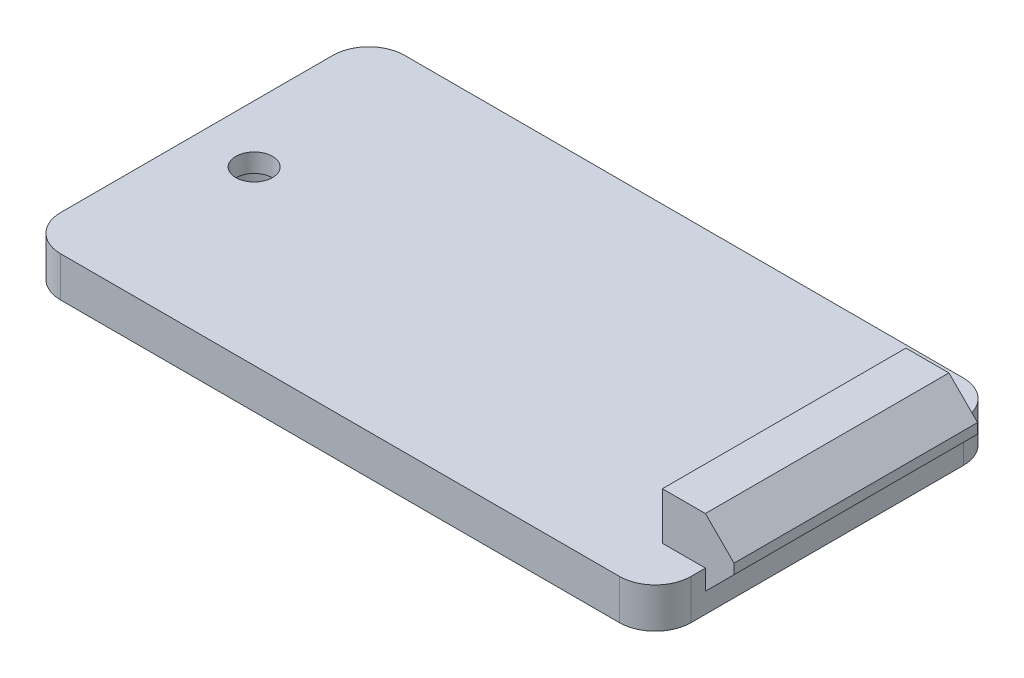
SolidWorks part; units mm, degrees
ref_plane "Front Plane" through (0, 0, 0) normal (0, 0, 1) x (1, 0, 0)
ref_plane "Top Plane" through (0, 0, 0) normal (0, 1, 0) x (1, 0, 0)
ref_plane "Right Plane" through (0, 0, 0) normal (1, 0, 0) x (0, 0, -1)
sketch "Sketch1" plane through (0, 0, 0) normal (0, 1, 0) x (1, 0, 0)
  line L0 (0, 15.24) -> (55.88, 15.24) construction
  line L1 (3.175, 0) -> (52.705, 0)
  line L2 (0, 3.175) -> (0, 27.305)
  line L3 (3.175, 30.48) -> (52.705, 30.48)
  line L4 (55.88, 3.175) -> (55.88, 27.305)
  arc A0 (3.175, 30.48) -> (0, 27.305) centre (3.175, 27.305) ccw
  arc A1 (55.88, 27.305) -> (52.705, 30.48) centre (52.705, 27.305) ccw
  arc A2 (52.705, 0) -> (55.88, 3.175) centre (52.705, 3.175) ccw
  arc A3 (0, 3.175) -> (3.175, 0) centre (3.175, 3.175) ccw
  circle A4 centre (5.08, 15.24) radius 1.632
  dimension "D3" = 6.35
  dimension "D1" = 3.2639
  dimension "D2" = 5.08
  dimension "D4" = 3.175
  dimension "D5" = 3.175
  dimension "D6" = 49.53
  dimension "D7" = 24.13
extrude "Boss-Extrude1" add sketch "Sketch1" along normal blind 3.556
sketch "Sketch2" plane through (0, 0, 0) normal (0, -1, 0) x (1, 0, 0)
  circle A0 centre (5.08, -15.24) radius 3.175
  circle A1 centre (5.08, -15.24) radius 1.6319
  dimension "D1" = 6.35
extrude "Cut-Extrude1" cut sketch "Sketch2" against normal blind 1.905
sketch "Sketch3" plane through (55.88, 0, 0) normal (1, 0, 0) x (0, 0, -1)
  line L0 (3.175, 3.556) -> (3.175, 0) construction
  line L1 (4.445, 1.5875) -> (26.035, 1.5875)
  line L2 (4.445, 1.5875) -> (4.445, 7.9375)
  line L3 (4.445, 7.9375) -> (26.035, 7.9375)
  line L4 (26.035, 1.5875) -> (26.035, 7.9375)
  line L5 (27.305, 3.556) -> (27.305, 0) construction
  line L6 (3.175, 0) -> (27.305, 0) construction
  dimension "D1" = 1.27
  dimension "D2" = 1.27
  dimension "D3" = 1.5875
  dimension "D4" = 6.35
extrude "Boss-Extrude2" add sketch "Sketch3" along normal blind 2.54
chamfer "Chamfer1" distance 2.7305 angle 45 2 edges at (58.42, 1.5875, -15.24) (58.42, 7.9375, -15.24)
sketch "Sketch4" plane through (55.88, 0, 0) normal (-1, 0, 0) x (0, 0, 1)
  line L5 (-26.035, 7.747) -> (-4.445, 7.747)
  line L6 (-26.035, 7.747) -> (-26.035, 3.556)
  line L7 (-26.035, 3.556) -> (-4.445, 3.556)
  line L8 (-4.445, 7.747) -> (-4.445, 3.556)
extrude "Boss-Extrude3" add sketch "Sketch4" along normal blind 3.81
sketch "Sketch5" plane through (0, 0, 0) normal (0, -1, 0) x (1, 0, 0)
  line L0 (12.7, -9.9279) -> (12.7, -30.48) construction
  line L2 (52.705, -30.48) -> (3.175, -30.48) construction
  line L3 (0, -27.305) -> (0, -3.175) construction
  line L4 (0, -15.24) -> (55.88, -15.24) construction
  line L5 (55.88, -26.035) -> (55.88, -4.445) construction
  line L6 (11.1125, -8.89) -> (11.1433, -21.9013)
  line L7 (14.2875, -8.89) -> (14.2567, -21.9013)
  arc A0 (14.2875, -8.89) -> (11.1125, -8.89) centre (12.7, -8.89) ccw
  arc A1 (11.1433, -21.9013) -> (14.2567, -21.9013) centre (12.7, -21.59) ccw
  dimension "D2" = 3.175
  dimension "D3" = 3.175
  dimension "D1" = 12.7
  dimension "D4" = 12.7
  dimension "D5" = 6.35
extrude "Cut-Extrude2" cut sketch "Sketch5" against normal blind 1.778
sketch "Sketch6" plane through (0, 0, 0) normal (0, -1, 0) x (1, 0, 0)
  line L0 (14.2807, -11.7475) -> (55.88, -11.7475) construction
  line L1 (14.2567, -21.9013) -> (14.2875, -8.89) construction
  line L2 (55.88, -26.035) -> (55.88, -4.445) construction
  line L3 (52.705, -30.48) -> (3.175, -30.48) construction
  text T0 "<b>PROGRAM</b>" font "Unispace" height 6.35
  dimension "D1" = 18.7325
extrude "Cut-Extrude3" cut sketch "Sketch6" against normal blind 0.635
